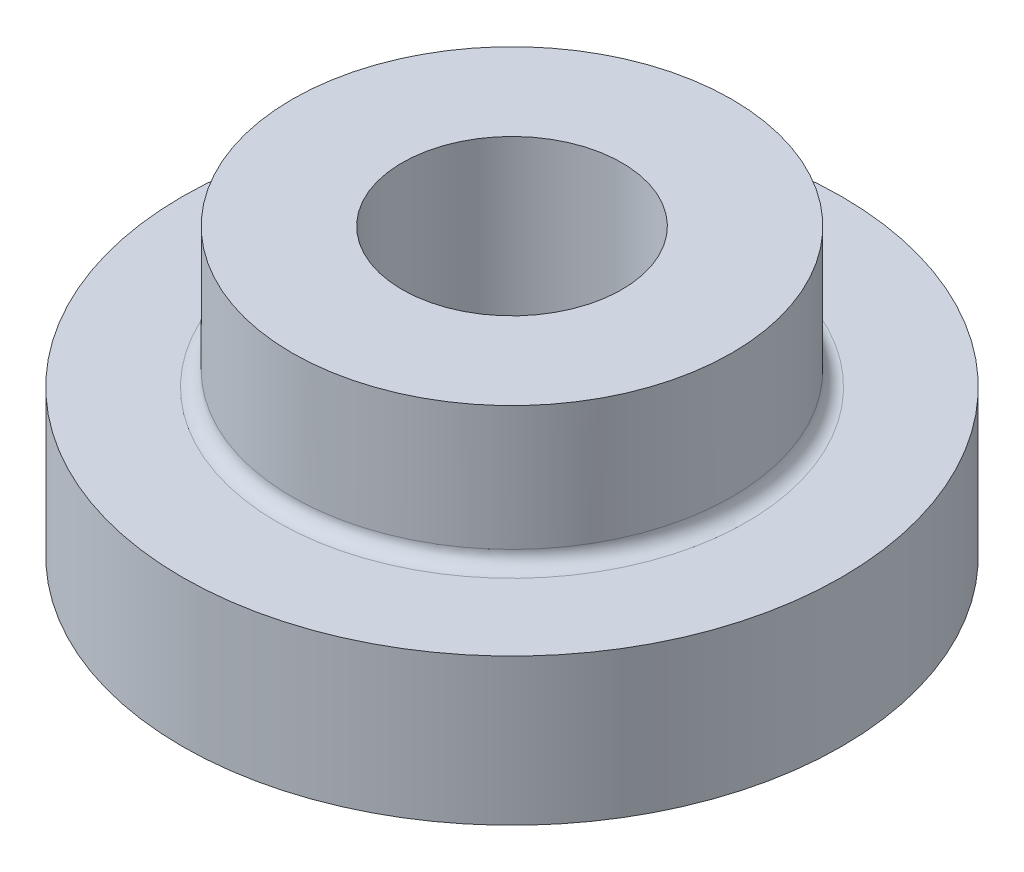
SolidWorks part; units mm, degrees
ref_plane "Front Plane" through (0, 0, 0) normal (0, 0, 1) x (1, 0, 0)
ref_plane "Top Plane" through (0, 0, 0) normal (0, 1, 0) x (1, 0, 0)
ref_plane "Right Plane" through (0, 0, 0) normal (1, 0, 0) x (0, 0, -1)
sketch "Sketch1" plane through (0, 0, 0) normal (0, 1, 0) x (1, 0, 0)
  circle A0 centre (0, 0) radius 3
  dimension "D1" = 6
extrude "Boss-Extrude1" add sketch "Sketch1" along normal blind 2.3
shell "Shell1" thickness 1.5 removed face at (0, 0, 3) removed face at (0, 2.3, 3)
sketch "Sketch2" plane through (0, 0, 0) normal (0, -1, 0) x (1, 0, 0)
  circle A0 centre (0, 0) radius 3 construction
  circle A1 centre (0, 0) radius 3
  circle A2 centre (0, 0) radius 4.5
  dimension "D1" = 1.5
extrude "Boss-Extrude2" add sketch "Sketch2" along normal blind 1.6 and the other way blind 0.4
fillet "Fillet4" radius 0.2 2 edges at (0, 0, 3) (0, 0.4, -3)
